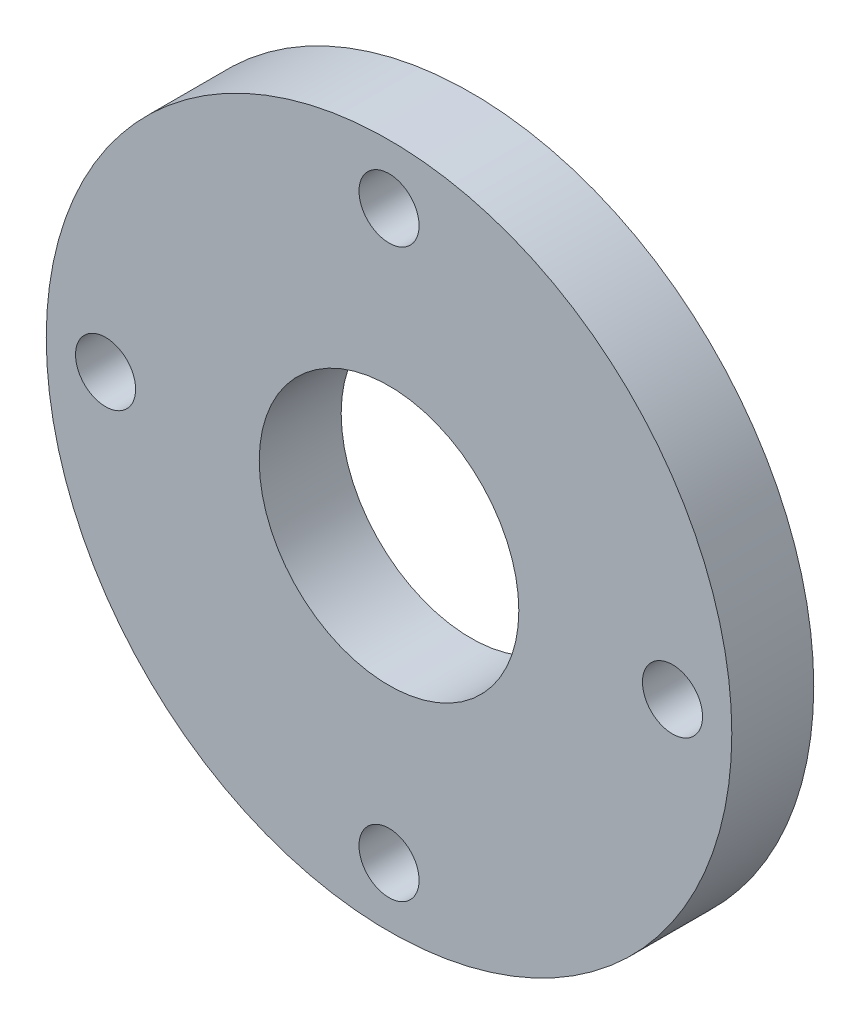
SolidWorks part; units mm, degrees
material "6061-T6 (SS)"
ref_plane "Front Plane" through (0, 0, 0) normal (0, 0, 1) x (1, 0, 0)
ref_plane "Top Plane" through (0, 0, 0) normal (0, 1, 0) x (1, 0, 0)
ref_plane "Right Plane" through (0, 0, 0) normal (1, 0, 0) x (0, 0, -1)
sketch "Sketch1" plane through (0, 0, 0) normal (1, 0, 0) x (0, 0, -1)
  line L0 (-119.6, -9.5) -> (-164, -9.5)
  line L5 (-1000, 0) -> (49000, 0)
  line L6 (0, -9.5) -> (0, 9.5)
  line L13 (0, 9.5) -> (-46.4, 9.5)
  line L26 (-46.4, 9.5) -> (-46.4, 14)
  line L27 (-46.4, 14) -> (-119.6, 14)
  line L32 (-119.6, 14) -> (-119.6, 9.5)
  line L34 (-180, 7) -> (-180, -7)
  line L36 (-119.6, -9.5) -> (-119.6, -14)
  line L37 (-119.6, -14) -> (-46.4, -14)
  line L38 (-46.4, -14) -> (-46.4, -9.5)
  line L39 (0, -9.5) -> (-46.4, -9.5)
  line L40 (-24.625, 37.6491) -> (-15.625, 37.6491)
  line L41 (-136.2, 22.6187) -> (-119.6, 22.6187)
  line L42 (-136.2, 22.6187) -> (-136.2, -22.6187)
  line L43 (-136.2, -22.6187) -> (-119.6, -22.6187)
  line L44 (-119.6, 22.6187) -> (-119.6, -22.6187)
  line L45 (-136.2, 22.6187) -> (-119.6, -22.6187) construction
  line L46 (-136.2, -22.6187) -> (-119.6, 22.6187) construction
  line L47 (-29.8, 22.6187) -> (-46.4, 22.6187)
  line L48 (-29.8, 22.6187) -> (-29.8, -22.6187)
  line L49 (-29.8, -22.6187) -> (-46.4, -22.6187)
  line L50 (-46.4, 22.6187) -> (-46.4, -22.6187)
  line L51 (-29.8, 22.6187) -> (-46.4, -22.6187) construction
  line L52 (-29.8, -22.6187) -> (-46.4, 22.6187) construction
  line L59 (-15.625, 37.6491) -> (-15.625, -37.6491)
  line L60 (-15.625, -37.6491) -> (-24.625, -37.6491)
  line L61 (-24.625, -22.6187) -> (-26.625, -22.6187)
  line L62 (-26.625, -22.6187) -> (-26.625, -12.5)
  line L63 (-26.625, -12.5) -> (-24.625, -12.5)
  line L64 (-24.625, -12.5) -> (-24.625, 12.5)
  line L65 (-24.625, 12.5) -> (-26.625, 12.5)
  line L66 (-26.625, 12.5) -> (-26.625, 22.6187)
  line L67 (-26.625, 22.6187) -> (-24.625, 22.6187)
  line L68 (-24.625, 22.6187) -> (-24.625, 37.6491)
  line L69 (-24.625, -22.6187) -> (-24.625, -37.6491)
  line L71 (-147.884, 37.6491) -> (-25.625, 37.6491)
  line L72 (-147.884, 37.6491) -> (-147.884, -37.6491)
  line L73 (-147.884, -37.6491) -> (-25.625, -37.6491)
  line L74 (-25.625, 37.6491) -> (-25.625, -37.6491)
  line L75 (-147.884, 37.6491) -> (-25.625, -37.6491) construction
  line L76 (-147.884, -37.6491) -> (-25.625, 37.6491) construction
  line L77 (-164, -9.5) -> (-164, -7)
  line L78 (-164, -7) -> (-180, -7)
  line L79 (-119.6, 9.5) -> (-164, 9.5)
  line L80 (-164, 7) -> (-180, 7)
  line L81 (-164, 9.5) -> (-164, 7)
  line L82 (-141.8, 9.5) -> (-141.8, -9.5) construction
  line L83 (-23.2, 9.5) -> (-23.2, -9.5) construction
  line L96 (-147.884, 37.6492) -> (-156.884, 37.6492)
  line L98 (-147.884, -37.6491) -> (-156.884, -37.6491)
  line L99 (-156.884, 37.6492) -> (-156.884, -37.6491)
  line L110 (-147.884, 37.6492) -> (-147.884, -37.6491)
  point P3 (0, 0)
  point P18 (-127.9, 0)
  point P24 (-38.1, 0)
  point P29 (-86.7545, 0)
  point P48 (-15.625, 31.1339)
  point P70 (-156.884, 31.1339)
revolve "Main_body" add sketch "Sketch1" angle 360 about L5 region at (0, 23.5746, 152.384)
sketch "Sketch5" plane through (0, 0, 156.884) normal (0, 0, 1) x (1, 0, 0)
  circle A0 centre (0, 0) radius 14.2558
  dimension "D1" = 28.5115
extrude "seal_seat" cut sketch "Sketch5" against normal through all
hole_wizard "M6 Clearance Hole1" positions "Sketch3" profile "Sketch4" hole size "M6" standard "ANSI Metric" end condition through all
sketch "Sketch3" plane through (0, 0, 156.884) normal (0, 0, 1) x (1, 0, 0)
  point P0 (0, 31.1339)
sketch "Sketch4" plane through (0, 31.1339, 156.884) normal (1, 0, 0) x (0, -1, 0)
  line L0 (0, 0) -> (0, 9)
  line L1 (0, 9) -> (3.3, 9)
  line L2 (3.3, 9) -> (3.3, 0)
  line L5 (3.3, 0) -> (0, 0)
  line L11 (0, -6.35) -> (0, 107.95) construction
  dimension "Thru Hole Dia." = 6.6
  dimension "Thru Hole Depth" = 9
pattern_circular "CirPattern1" count 4 over 360 about axis through (0, 0, 1000) along (0, 0, -1) of "M6 Clearance Hole1"
